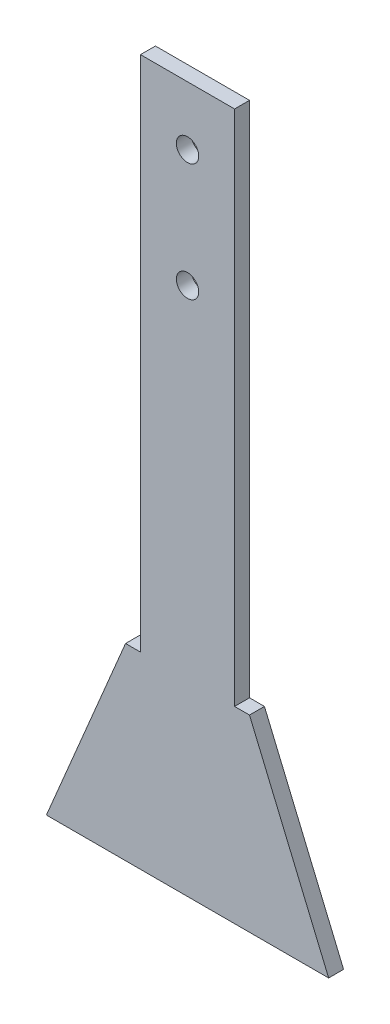
SolidWorks part; units mm, degrees
material "ABS"
ref_plane "Plan de face" through (0, 0, 0) normal (0, 0, 1) x (1, 0, 0)
ref_plane "Plan de dessus" through (0, 0, 0) normal (0, 1, 0) x (1, 0, 0)
ref_plane "Plan de droite" through (0, 0, 0) normal (1, 0, 0) x (0, 0, -1)
sketch "Esquisse1" plane through (0, 0, 0) normal (0, 0, 1) x (1, 0, 0)
  line L1 (-20, 300) -> (20, 300)
  line L2 (-20, 300) -> (-20, 80)
  line L4 (20, 300) -> (20, 80)
  line L8 (-60, 0) -> (60, 0)
  line L9 (26.35, 80) -> (-26.35, 80) construction
  line L10 (26.35, 80) -> (60, 0)
  line L11 (-26.35, 80) -> (-60, 0)
  line L12 (26.35, 80) -> (20, 80)
  line L13 (-20, 80) -> (-26.35, 80)
  point P1 (0, 0)
  point P2 (0, 300)
  point P8 (0, 80)
  dimension "D1" = 80
  dimension "D2" = 120
  dimension "D3" = 40
  dimension "D4" = 300
  dimension "D5" = 6.35
extrude "Boss.-Extru.1" add sketch "Esquisse1" along normal blind 6.35
sketch "Sketch1" plane through (0, 0, 6.35) normal (0, 0, 1) x (1, 0, 0)
  line L0 (20, 300) -> (-20, 300) construction
  circle A0 centre (0, 275) radius 4.7625
  circle A1 centre (0, 225) radius 4.7625
  point P6 (0, 300)
  dimension "D2" = 25
  dimension "D3" = 9.525
  dimension "D1" = 50
extrude "Cut-Extrude1" cut sketch "Sketch1" against normal up to surface (6.35 mm away) up to face at (0, 115, 0)
